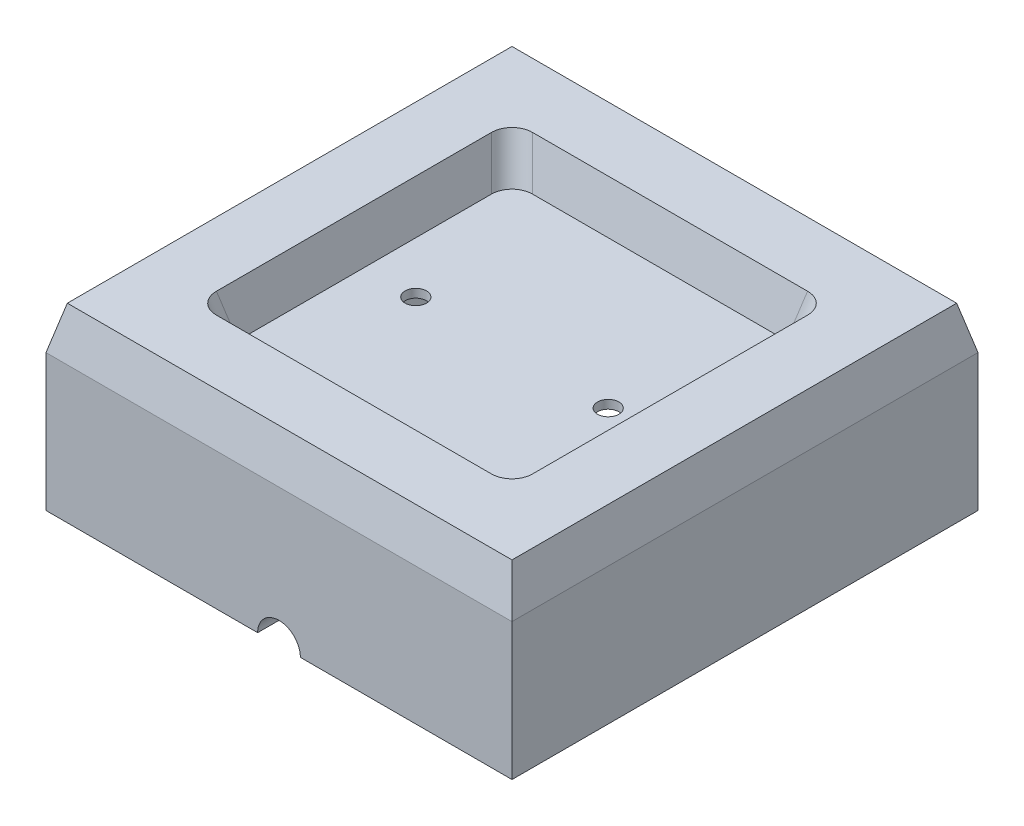
SolidWorks part; units mm, degrees
ref_plane "Front Plane" through (0, 0, 0) normal (0, 0, 1) x (1, 0, 0)
ref_plane "Top Plane" through (0, 0, 0) normal (0, 1, 0) x (1, 0, 0)
ref_plane "Right Plane" through (0, 0, 0) normal (1, 0, 0) x (0, 0, -1)
sketch "Sketch1" plane through (0, 0, 0) normal (0, 1, 0) x (1, 0, 0)
  line L1 (-34.5, -34.5) -> (34.5, -34.5)
  line L2 (-34.5, -34.5) -> (-34.5, 34.5)
  line L3 (-34.5, 34.5) -> (34.5, 34.5)
  line L4 (34.5, -34.5) -> (34.5, 34.5)
  line L5 (-34.5, -34.5) -> (34.5, 34.5) construction
  line L6 (-34.5, 34.5) -> (34.5, -34.5) construction
  point P0 (0, 0)
  dimension "D1" = 69
ref_plane "Plane1" through (0, 10, 0) normal (0, 1, 0) x (1, 0, 0)
extrude "Extrude-Thin1" add sketch "Sketch1" along normal blind 10 draft 14 thin thin type one direction wall 20
fillet "Fillet1" radius 5 4 edges at (35.7466, 5, 35.7466) (35.7466, 5, -35.7466) (-35.7466, 5, -35.7466) (-35.7466, 5, 35.7466)
sketch "Sketch3" plane through (0, 0, 0) normal (0, -1, 0) x (1, 0, 0)
  line L4 (54.5, -54.5) -> (54.5, 54.5)
  line L5 (54.5, 54.5) -> (-54.5, 54.5)
  line L6 (-54.5, 54.5) -> (-54.5, -54.5)
  line L7 (-54.5, -54.5) -> (54.5, -54.5)
  line L8 (54.5, -54.5) -> (54.5, 54.5)
  line L9 (54.5, 54.5) -> (-54.5, 54.5)
  line L10 (-54.5, 54.5) -> (-54.5, -54.5)
  line L11 (-54.5, -54.5) -> (54.5, -54.5)
  dimension "D1" = 0
extrude "Boss-Extrude1" add sketch "Sketch3" along normal blind 2
sketch "Sketch4" plane through (0, 0, 0) normal (0, 1, 0) x (1, 0, 0)
  line L0 (-2.9848, 0) -> (-16.8616, 0) construction
  circle A0 centre (-22.5, 0) radius 2.5
  point P2 (0, 0)
  point P7 (0, 0)
  dimension "D1" = 5
  dimension "D2" = 22.5
extrude "Cut-Extrude1" cut sketch "Sketch4" against normal up to surface (2 mm away) up to face at (0, -2, 0)
ref_plane "Plane2" through (0, 0, 0) normal (1, 0, 0) x (0, 0, -1)
mirror "Mirror1" about plane through (0, 0, 0) normal (1, 0, 0) of "Cut-Extrude1"
sketch "Sketch5" plane through (0, -2, 0) normal (0, -1, 0) x (1, 0, 0)
  line L1 (-54.5, -54.5) -> (54.5, -54.5) construction
  line L2 (54.5, -54.5) -> (54.5, 54.5) construction
  line L3 (54.5, 54.5) -> (-54.5, 54.5) construction
  line L4 (-54.5, 54.5) -> (-54.5, -54.5) construction
  line L5 (-54.5, -54.5) -> (54.5, -54.5)
  line L6 (54.5, -54.5) -> (54.5, 54.5)
  line L7 (54.5, 54.5) -> (-54.5, 54.5)
  line L8 (-54.5, 54.5) -> (-54.5, -54.5)
extrude "Extrude-Thin2" add sketch "Sketch5" along normal blind 30 thin thin type one direction reverse wall 5
sketch "Sketch6" plane through (0, 0, 54.5) normal (0, 0, 1) x (1, 0, 0)
  line L0 (54.5, -32) -> (-54.5, -32) construction
  line L1 (-5, -32) -> (5, -32)
  arc A0 (-5, -32) -> (5, -32) centre (0, -32) cw
  dimension "D1" = 5
extrude "Cut-Extrude2" cut sketch "Sketch6" against normal up to surface (5 mm away) up to face at (0, -17, 49.5)
